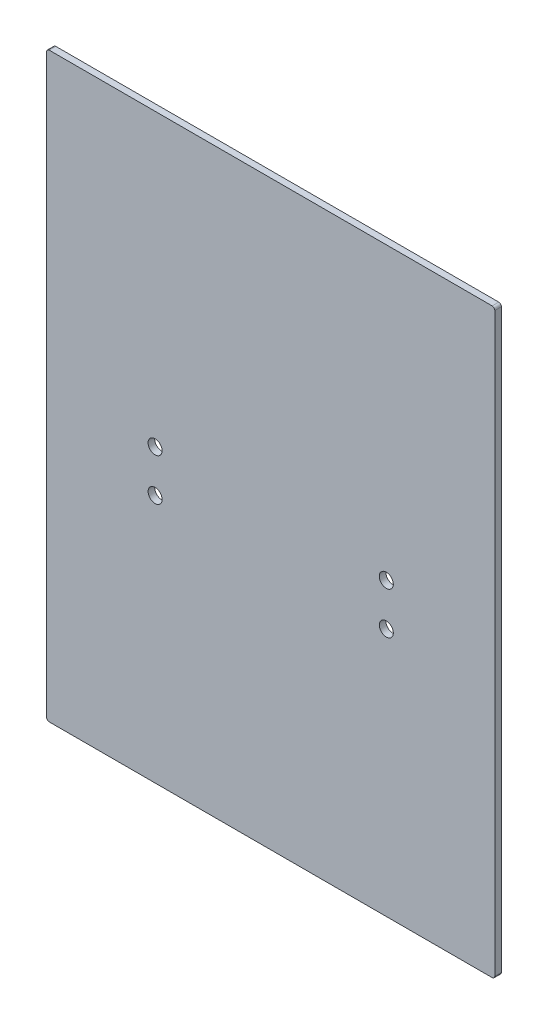
SolidWorks part; units mm, degrees
material "Plain Carbon Steel"
ref_plane "Front Plane" through (0, 0, 0) normal (0, 0, 1) x (1, 0, 0)
ref_plane "Top Plane" through (0, 0, 0) normal (0, 1, 0) x (1, 0, 0)
ref_plane "Right Plane" through (0, 0, 0) normal (1, 0, 0) x (0, 0, -1)
sketch "Sketch1" plane through (0, 0, 0) normal (0, 0, 1) x (1, 0, 0)
  line L0 (355.6, -484.2272) -> (0, 0) construction
  line L1 (0, 0) -> (0, 38.1) construction
  line L2 (393.7, -522.3669) -> (-38.1, -522.3669)
  line L3 (393.7, -522.3669) -> (393.7, 38.1)
  line L4 (393.7, 38.1) -> (-38.1, 38.1)
  line L5 (-38.1, -522.3669) -> (-38.1, 38.1)
  line L6 (393.7, -522.3669) -> (-38.1, 38.1) construction
  line L7 (393.7, 38.1) -> (-38.1, -522.3669) construction
  line L8 (-25.4, -21.4312) -> (-25.4, 21.4312) construction
  line L9 (0, 0) -> (-38.1, 0) construction
  point P4 (177.8, -242.1334)
  dimension "D1" = 12.7
extrude "Boss-Extrude1" add sketch "Sketch1" along normal blind 6.35
fillet "Fillet1" radius 2.54 4 edges at (393.7, 38.1, 3.175) (393.7, -522.3669, 3.175) (-38.1, -522.3669, 3.175) (-38.1, 38.1, 3.175)
sketch "Sketch3" plane through (0, 0, 0) normal (0, 0, -1) x (-1, 0, 0)
  line L0 (-177.8, 38.1) -> (-177.8, -522.3669) construction
  line L1 (-391.16, 38.1) -> (35.56, 38.1) construction
  line L2 (35.56, -522.3669) -> (-391.16, -522.3669) construction
  line L3 (-177.8, -262.14) -> (-289.1714, -262.14) construction
  line L4 (-289.1714, -241.82) -> (-289.1714, -282.46) construction
  point P8 (-289.1714, -241.82)
  point P9 (-289.1714, -282.46)
  point P13 (-66.4286, -282.46)
  point P14 (-66.4286, -241.82)
  dimension "D1" = 40.64
  dimension "D2" = 279.92
  dimension "D3" = 222.7428
hole_wizard "1/2 Clearance Hole1" positions "Sketch3" profile "Sketch4" hole size "1/2" standard "ANSI Inch" end condition up to next
sketch "Sketch4" plane through (66.4286, -241.82, 0) normal (1, 0, 0) x (0, 1, 0)
  line L0 (0, 0) -> (0, 6.35)
  line L1 (0, 6.35) -> (6.7462, 6.35)
  line L2 (6.7462, 6.35) -> (6.7462, 0)
  line L5 (6.7462, 0) -> (0, 0)
  line L11 (0, -6.35) -> (0, 107.95) construction
  dimension "Thru Hole Dia." = 13.4925
  dimension "Thru Hole Depth" = 6.35
